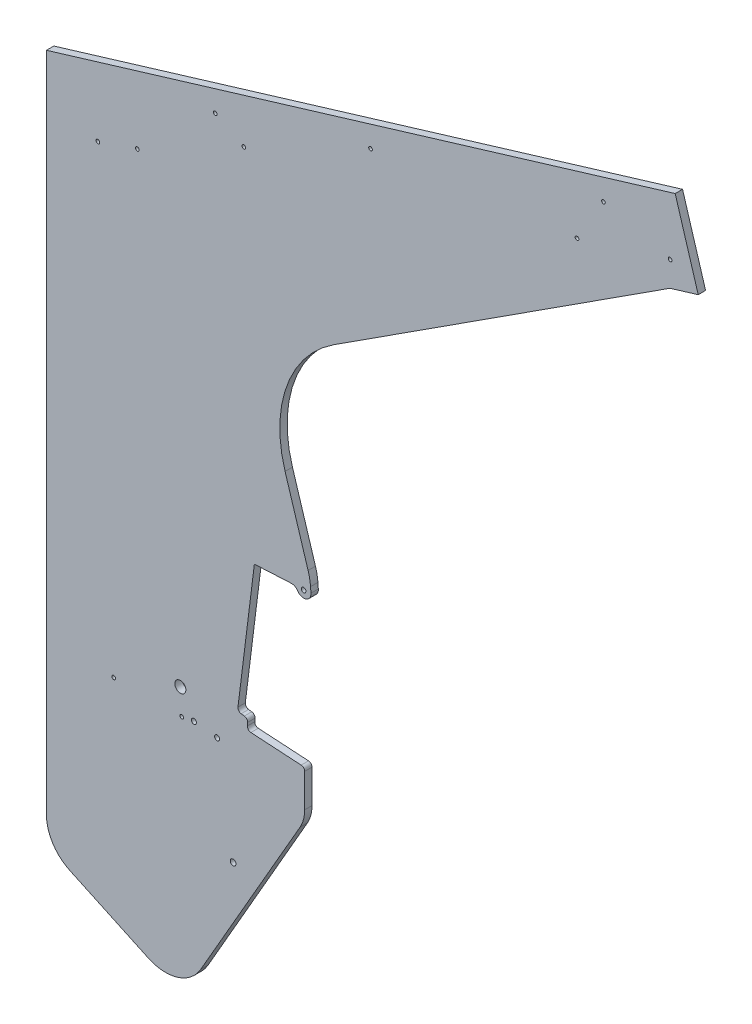
SolidWorks part; units mm, degrees
material "Beech"
ref_plane "Front Plane" through (0, 0, 0) normal (0, 0, 1) x (1, 0, 0)
ref_plane "Top Plane" through (0, 0, 0) normal (0, 1, 0) x (1, 0, 0)
ref_plane "Right Plane" through (0, 0, 0) normal (1, 0, 0) x (0, 0, -1)
sketch "Sketch1" plane through (0, 0, 0) normal (0, 0, 1) x (1, 0, 0)
  line L14 (109.0999, 158.659) -> (398.6241, 345.5216)
  line L15 (398.6241, 345.5216) -> (422.935, 352.8794)
  line L16 (422.935, 352.8794) -> (403.0991, 418.4193)
  line L17 (403.0991, 418.4193) -> (-138.3789, 254.5381)
  line L18 (-138.3789, 254.5381) -> (-138.3789, -315.4534)
  line L19 (-118.2139, -347.1062) -> (-50.5059, -378.6789)
  line L21 (-5.4671, -364.4315) -> (80.009, -215.7351)
  line L22 (84, -200.7842) -> (84, -156.3804)
  line L23 (84, -156.3804) -> (45.8908, -155.3854)
  line L24 (45.8908, -155.3854) -> (48.6774, -48.6606)
  line L25 (48.6774, -48.6606) -> (90.1605, -46.0697)
  line L26 (90.1605, -46.0697) -> (89.0709, -31.7487)
  line L27 (86.9733, -20.7388) -> (67.1502, 43.2142)
  arc A2 (80.009, -215.7351) -> (84, -200.7842) centre (54, -200.7842) ccw
  arc A7 (-138.3789, -315.4534) -> (-118.2139, -347.1062) centre (-103.4539, -315.4534) ccw
  arc A9 (89.0709, -31.7487) -> (86.9733, -20.7388) centre (39.215, -35.5422) ccw
  arc A10 (109.0999, 158.659) -> (67.1502, 43.2142) centre (164.1952, 73.2946) ccw
  arc A11 (-50.5059, -378.6789) -> (-5.4671, -364.4315) centre (-35.746, -347.0261) ccw
  dimension "D2" = 101.6
  dimension "D3" = 34.925
extrude "Boss-Extrude1" add sketch "Sketch1" along normal blind 6.35
sketch "Sketch2" plane through (0, 0, 6.35) normal (0, 0, 1) x (1, 0, 0)
  circle A1 centre (83.098, -37.255) radius 2
extrude "Cut-Extrude1" cut sketch "Sketch2" against normal through all
sketch "Sketch3" plane through (0, 0, 6.35) normal (0, 0, 1) x (1, 0, 0)
  line L0 (84, -156.3804) -> (45.8908, -155.3854) construction
  line L1 (45.8908, -155.3854) -> (48.6774, -48.6606) construction
  line L2 (48.6774, -48.6606) -> (90.1605, -46.0697) construction
  line L3 (34.5371, -166.0421) -> (35.0858, -157.1104)
  line L4 (35.0858, -157.1104) -> (26.1865, -156.0047)
  line L5 (84, -169.0804) -> (84, -156.3804)
  line L6 (84, -156.3804) -> (45.8908, -155.3854)
  line L7 (45.8908, -155.3854) -> (48.6774, -48.6606)
  line L8 (48.6774, -48.6606) -> (90.1605, -46.0697)
  line L9 (90.1605, -46.0697) -> (89.9196, -42.9035)
  line L10 (89.9196, -42.9035) -> (77.2443, -43.6952)
  line L11 (77.2443, -43.6952) -> (76.92, -37.3323)
  line L12 (76.92, -37.3323) -> (40.7015, -39.1783)
  line L13 (40.7015, -39.1783) -> (26.1865, -156.0047)
  line L14 (34.5371, -166.0421) -> (84, -169.0804)
  dimension "D1" = 12.7
  dimension "D2" = 3.175
  dimension "D3" = 12.7
extrude "Cut-Extrude2" cut sketch "Sketch3" against normal up to next
fillet "Fillet4" radius 6.35 2 edges at (77.2443, -43.6952, 3.175) (89.9196, -42.9035, 3.175)
fillet "Fillet5" radius 6.35 1 edges at (76.92, -37.3323, 3.175)
fillet "Fillet6" radius 3.175 4 edges at (84, -169.0804, 3.175) (34.5371, -166.0421, 3.175) (35.0858, -157.1104, 3.175) (26.1865, -156.0047, 3.175)
hole_wizard "#8 Clearance Hole1" positions "Sketch4" profile "Sketch5" hole size "#8" standard "ANSI Inch" end condition through all
sketch "Sketch4" plane through (0, 0, 0) normal (0, 0, -1) x (-1, 0, 0)
  circle A0 centre (-22.4173, -270.7692) radius 2.4574 construction
  point P1 (-22.4173, -270.7692)
sketch "Sketch5" plane through (22.4173, -270.7692, 0) normal (1, 0, 0) x (0, 1, 0)
  line L0 (0, 0) -> (0, 6.35)
  line L1 (0, 6.35) -> (2.4574, 6.35)
  line L2 (2.4574, 6.35) -> (2.4574, 0)
  line L5 (2.4574, 0) -> (0, 0)
  line L11 (0, -6.35) -> (0, 107.95) construction
  dimension "Thru Hole Dia." = 4.9149
  dimension "Thru Hole Depth" = 6.35
hole_wizard "Hole1" positions "Sketch6" profile "Sketch7" legacy
sketch "Sketch6" plane through (-267.4108, -204.0765, 12.7) normal (0, 0, 1) x (-0.09, -0.9959, 0)
  point P4 (-507.0387, 229.7761)
  point P6 (-559.3712, 359.3037)
  point P8 (-637.87, 553.5951)
  point P10 (-628.7751, 612.0592)
  point P12 (-597.3958, 534.3927)
  point P16 (-496.527, 255.4282)
  point P18 (-441.05, 168.3613)
  point P20 (-426.601, 135.516)
  point P22 (-41.7953, 242.7611)
  point P24 (-36.5327, 184.4983)
  point P27 (0, 0)
sketch "Sketch7" plane through (7.0467, 280.2357, 12.7) normal (1, 0, 0) x (0, -1, 0)
  line L0 (0, 0) -> (0, 32.7039)
  line L1 (0, 32.7039) -> (1.5875, 31.75)
  line L2 (1.5875, 31.75) -> (1.5875, 4.0177)
  line L3 (1.5875, 4.0177) -> (5.08, 0)
  line L4 (5.08, 0) -> (0, 0)
  line L5 (0, -14.3089) -> (0, 102.4216) construction
  line L6 (0, 32.7039) -> (-1.5875, 31.75) construction
  line L7 (-1.5875, 4.0177) -> (-5.08, 0) construction
  dimension "Diameter" = 3.175
  dimension "Depth" = 31.75
  dimension "C-Sink Diameter" = 10.16
  dimension "C-Sink Angle" = 82
  dimension "Drill Angle" = 118
hole_wizard "CSK for #6 Flat Head Machine Screw (100)1" positions "Sketch8" profile "Sketch9" countersink size "#6" standard "ANSI Inch" end condition up to next
sketch "Sketch8" plane through (0, 0, 0) normal (0, 0, -1) x (-1, 0, 0)
  point P0 (-8.6038, -184.7304)
  point P2 (11.3597, -182.482)
sketch "Sketch9" plane through (8.6038, -184.7304, 0) normal (1, 0, 0) x (0, 1, 0)
  line L0 (0, 0) -> (0, 6.35)
  line L1 (0, 6.35) -> (2.1526, 6.35)
  line L2 (2.1526, 6.35) -> (2.1526, 1.1669)
  line L3 (2.1526, 1.1669) -> (3.5433, 0)
  line L5 (3.5433, 0) -> (0, 0)
  line L6 (-2.1526, 1.1669) -> (-3.5433, 0) construction
  line L11 (0, -6.35) -> (0, 107.95) construction
  dimension "Thru Hole Dia." = 4.3053
  dimension "Thru Hole Depth" = 6.35
  dimension "Near C'Sink Dia." = 7.0866
  dimension "Near C'Sink Angle" = 100
hole_wizard "3/8 (0.375) Diameter Hole1" positions "Sketch10" profile "Sketch11" hole size "3/8" standard "ANSI Inch" end condition up to next
sketch "Sketch10" plane through (0, 0, 6.35) normal (0, 0, 1) x (1, 0, 0)
  point P0 (-23.0396, -162.5135)
sketch "Sketch11" plane through (-23.0396, -162.5135, 6.35) normal (1, 0, 0) x (0, -1, 0)
  line L0 (0, 0) -> (0, 6.35)
  line L1 (0, 6.35) -> (4.7625, 6.35)
  line L2 (4.7625, 6.35) -> (4.7625, 0)
  line L5 (4.7625, 0) -> (0, 0)
  line L11 (0, -6.35) -> (0, 107.95) construction
  dimension "Thru Hole Dia." = 9.525
  dimension "Thru Hole Depth" = 6.35
